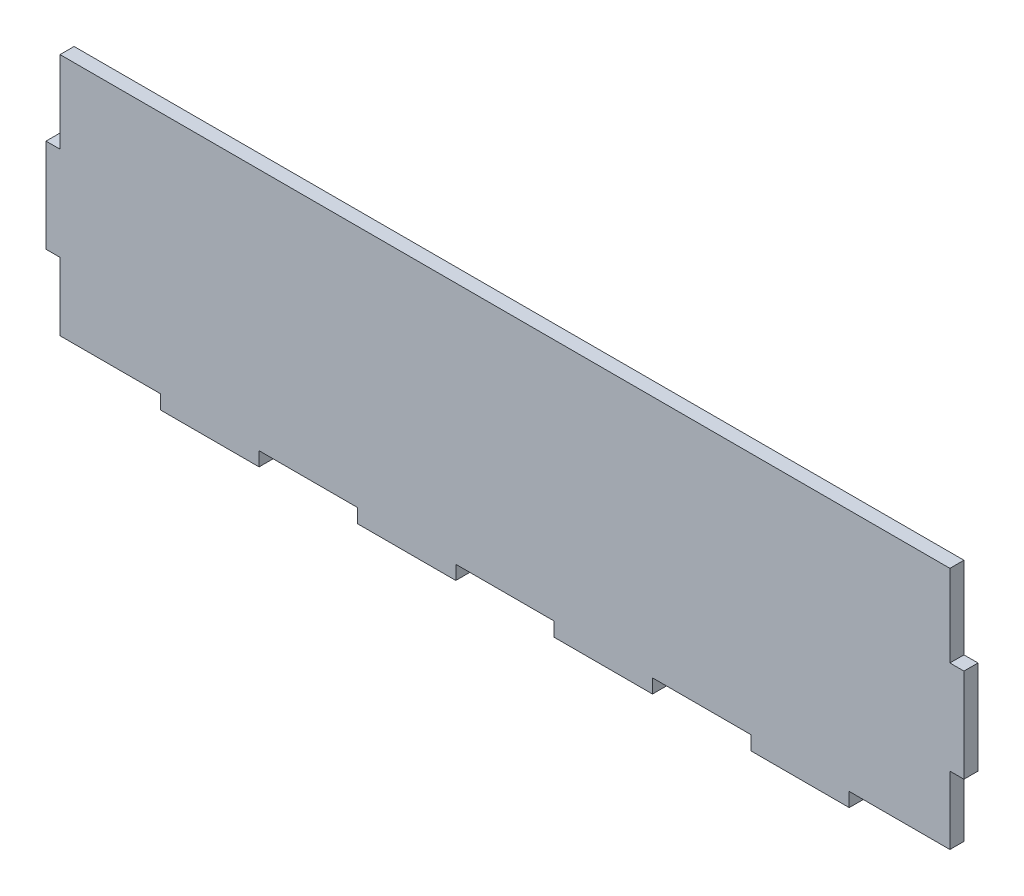
SolidWorks part; units mm, degrees
ref_plane "Front Plane" through (0, 0, 0) normal (0, 0, 1) x (1, 0, 0)
ref_plane "Top Plane" through (0, 0, 0) normal (0, 1, 0) x (1, 0, 0)
ref_plane "Right Plane" through (0, 0, 0) normal (1, 0, 0) x (0, 0, -1)
sketch "Sketch1" plane through (0, 0, 0) normal (0, 0, 1) x (1, 0, 0)
  line L0 (0, -24.5) -> (10.5, -24.5)
  line L1 (-98, -27.5) -> (98, -27.5)
  line L2 (-98, -27.5) -> (-98, 27.5)
  line L3 (-98, 27.5) -> (98, 27.5)
  line L4 (98, -27.5) -> (98, 27.5)
  line L5 (-98, -27.5) -> (98, 27.5) construction
  line L6 (-98, 27.5) -> (98, -27.5) construction
  line L7 (10.5, -24.5) -> (10.5, -27.5)
  line L8 (10.5, -27.5) -> (31.5, -27.5)
  line L9 (31.5, -27.5) -> (31.5, -24.5)
  line L10 (31.5, -24.5) -> (52.5, -24.5)
  line L11 (52.5, -24.5) -> (52.5, -27.5)
  line L12 (52.5, -27.5) -> (73.5, -27.5)
  line L13 (73.5, -27.5) -> (73.5, -24.5)
  line L14 (73.5, -24.5) -> (98, -24.5)
  line L15 (0, -24.5) -> (-10.5, -24.5)
  line L16 (-10.5, -24.5) -> (-10.5, -27.5)
  line L17 (-10.5, -27.5) -> (-31.5, -27.5)
  line L18 (-31.5, -27.5) -> (-31.5, -24.5)
  line L19 (-31.5, -24.5) -> (-52.5, -24.5)
  line L20 (-52.5, -24.5) -> (-52.5, -27.5)
  line L21 (-52.5, -27.5) -> (-73.5, -27.5)
  line L22 (-73.5, -27.5) -> (-73.5, -24.5)
  line L23 (-73.5, -24.5) -> (-98, -24.5)
  line L24 (-98, 10) -> (-95, 10)
  line L25 (-95, 10) -> (-95, 27.5)
  line L26 (-98, -10) -> (-95, -10)
  line L27 (-95, -10) -> (-95, -27.5)
  line L28 (95, 27.5) -> (95, 10)
  line L29 (95, 10) -> (98, 10)
  line L30 (98, 10) -> (98, -10)
  line L31 (98, -10) -> (95, -10)
  line L32 (95, -10) -> (95, -27.5)
  point P0 (0, 0)
  dimension "D1" = 55
  dimension "D2" = 196
  dimension "D3" = 10.5
  dimension "D4" = 0
  dimension "D5" = 10.5
  dimension "D6" = 21
  dimension "D7" = 21
  dimension "D8" = 21
  dimension "D9" = 21
  dimension "D10" = 21
  dimension "D11" = 21
  dimension "D12" = 3
  dimension "D13" = 3
  dimension "D14" = 3
  dimension "D15" = 20
  dimension "D16" = 17.5
  dimension "D17" = 3
  dimension "D18" = 3
  dimension "D19" = 3
  dimension "D20" = 3
extrude "Boss-Extrude1" add sketch "Sketch1" along normal blind 3 contours L23 L22 L1 L20 L19 L18 L16 L15 L0 L7 L9 L10 L11 L13 L14 L4 L3 L2 region at (0, 0.8065, 0)
